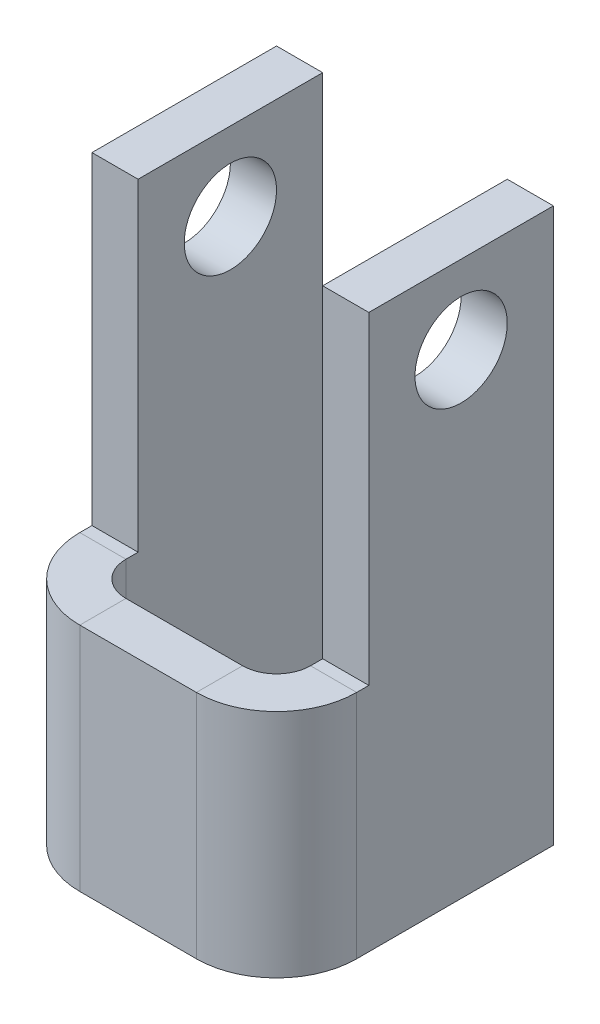
SolidWorks part; units mm, degrees
note: The reader was unsure of these and kept them because the rebuilt part matched: thickness of "Brida base1", "Brida de arista1", "Chapa metálica1", "Chapa metálica2", "Chapa metálica3", "Chapa metálica4"; flange length of "Brida de arista1".
ref_plane "Alzado" through (0, 0, 0) normal (0, 0, 1) x (1, 0, 0)
ref_plane "Planta" through (0, 0, 0) normal (0, 1, 0) x (1, 0, 0)
ref_plane "Vista lateral" through (0, 0, 0) normal (1, 0, 0) x (0, 0, -1)
sketch "Croquis2" plane through (0, 0, 0) normal (0, 0, 1) x (1, 0, 0)
  line L1 (0, 0) -> (6, 0)
  line L2 (0, 0) -> (0, 12)
  line L3 (0, 12) -> (6, 12)
  line L4 (6, 0) -> (6, 12)
  dimension "D1" = 6
  dimension "D2" = 12
base flange "Brida base1" sketch "Croquis2" thickness 1 reverse thickness direction no parameters "D1"=0.7366
edge flange "Brida de arista1" sketch "Croquis11" flange profiles "Croquis11", "Croquis12" flange angle 90 flange length 6 flange position material inside bend radius 0.7366 thickness 1 relief rectangular parameters "D6"=10, "D8"=0.5
sketch "Croquis11" plane through (6, 0, -1) normal (1, 0, 0) x (0, -1, 0)
  line L0 (0, 0) -> (-12, 0) construction
  line L1 (0, 0) -> (-12, 0)
  line L2 (-12, 0) -> (-12, 5)
  line L3 (-12, 5) -> (0, 5)
  line L4 (0, 5) -> (0, 0)
sketch "Croquis12" plane through (0, 0, -1) normal (-1, 0, 0) x (0, 1, 0)
  line L0 (12, 0) -> (0, 0) construction
  line L1 (12, 0) -> (0, 0)
  line L2 (0, 0) -> (0, 5)
  line L3 (0, 5) -> (12, 5)
  line L4 (12, 5) -> (12, 0)
bend "Pliegue de arista1" bend radius 0.7366 bend angle 90 parameters "D5"=1
bend "Pliegue de arista2" bend radius 0.7366 bend angle 90 parameters "D5"=2
sketch "Croquis13" plane through (6, 0, 0) normal (1, 0, 0) x (0, 0, -1)
  line L0 (6, 12) -> (1.7366, 12) construction
  line L1 (2, 12) -> (0, 12)
  line L2 (2, 12) -> (2, 5)
  line L3 (2, 5) -> (0, 5)
  line L4 (0, 12) -> (0, 5)
  line L5 (0, 0) -> (0, 12) construction
  dimension "D1" = 2
  dimension "D2" = 7
extrude "Cortar-Extruir1" cut sketch "Croquis13" against normal blind 10 normal cut yes
sketch "Croquis14" plane through (6, 0, 0) normal (1, 0, 0) x (0, 0, -1)
  line L0 (4, 12) -> (4, 10.3) construction
  line L1 (6, 12) -> (2, 12) construction
  circle A0 centre (4, 10.3) radius 1
  dimension "D2" = 2
  dimension "D1" = 1.7
extrude "Cortar-Extruir2" cut sketch "Croquis14" against normal up to surface (6 mm away) normal cut yes up to face at (0, 5.6667, -3.2455)
sketch "Líneas de pliegue1" [suppressed] plane through (0, 0, 0) normal (0, 1, 0) x (1, 0, 0)
sketch "Cuadro delimitador1" [suppressed] plane through (0, 0, 0) normal (0, 1, 0) x (1, 0, 0)
sheet metal parameters "Chapa metálica1" thickness 1 parameters "D1"=0.7366
flat pattern "Chapa desplegada1" [suppressed]
sketch "Líneas de pliegue2" plane through (0, 0, 0) normal (0, 1, 0) x (1, 0, 0)
sketch3d "Cuadro delimitador2" [suppressed]
  line L0 (-6, 12, 0) -> (-6, 0, 0) construction
  line L1 (0, 12, 0) -> (0, 0, 0) construction
  line L2 (-6, 12, 0) -> (0, 12, 0) construction
  line L3 (-6, 0, 0) -> (0, 0, 0) construction
sheet metal parameters "Chapa metálica2" thickness 1 parameters "D1"=0.7366, "D7"=1.5
flat pattern "Chapa desplegada1"
sketch "Líneas de pliegue2" plane through (0, 0, 0) normal (0, 0, 1) x (1, 0, 0)
  line L0 (1.069, 12) -> (1.069, 0) construction
  line L1 (4.931, 0) -> (4.931, 12) construction
  line L2 (1.069, 12) -> (1.069, 0) construction
  line L3 (4.931, 0) -> (4.931, 12) construction
sketch3d "Cuadro delimitador2" [suppressed]
  line L0 (-3.8619, 0, 0) -> (9.8619, 0, 0) construction
  line L1 (-3.8619, 12, 0) -> (9.8619, 12, 0) construction
  line L2 (-3.8619, 0, 0) -> (-3.8619, 12, 0) construction
  line L3 (9.8619, 0, 0) -> (9.8619, 12, 0) construction
bend of the flat pattern "Aplanar-<Pliegue de arista1>1"
bend of the flat pattern "Aplanar-<Pliegue de arista2>1"
sheet metal parameters "Chapa metálica3" thickness 1 parameters "D1"=0.7366, "D7"=1.5
flat pattern "Chapa desplegada1"
sketch "Líneas de pliegue2" plane through (0, 0, 0) normal (0, 0, 1) x (1, 0, 0)
  line L0 (0.7654, 5) -> (0.7654, 0) construction
  line L1 (5.2346, 0) -> (5.2346, 5) construction
  line L2 (0.7654, 5) -> (0.7654, 0) construction
  line L3 (5.2346, 0) -> (5.2346, 5) construction
sketch3d "Cuadro delimitador2" [suppressed]
  line L0 (-4.4692, 0, 0) -> (10.4692, 0, 0) construction
  line L1 (-4.4692, 12, 0) -> (10.4692, 12, 0) construction
  line L2 (-4.4692, 0, 0) -> (-4.4692, 12, 0) construction
  line L3 (10.4692, 0, 0) -> (10.4692, 12, 0) construction
bend of the flat pattern "Aplanar-<Pliegue de arista1>1"
bend of the flat pattern "Aplanar-<Pliegue de arista2>1"
sheet metal parameters "Chapa metálica4" thickness 1 parameters "D1"=0.7366, "D7"=1.5
flat pattern "Chapa desplegada1"
sketch "Líneas de pliegue2" plane through (0, 0, 0) normal (0, 0, 1) x (1, 0, 0)
  line L0 (0.7654, 5) -> (0.7654, 0) construction
  line L1 (5.2346, 0) -> (5.2346, 5) construction
  line L2 (0.7654, 5) -> (0.7654, 0) construction
  line L3 (5.2346, 0) -> (5.2346, 5) construction
sketch3d "Cuadro delimitador2" [suppressed]
  line L0 (-4.4692, 0, 0) -> (10.4692, 0, 0) construction
  line L1 (-4.4692, 12, 0) -> (10.4692, 12, 0) construction
  line L2 (-4.4692, 0, 0) -> (-4.4692, 12, 0) construction
  line L3 (10.4692, 0, 0) -> (10.4692, 12, 0) construction
bend of the flat pattern "Aplanar-<Pliegue de arista1>1"
bend of the flat pattern "Aplanar-<Pliegue de arista2>1"
